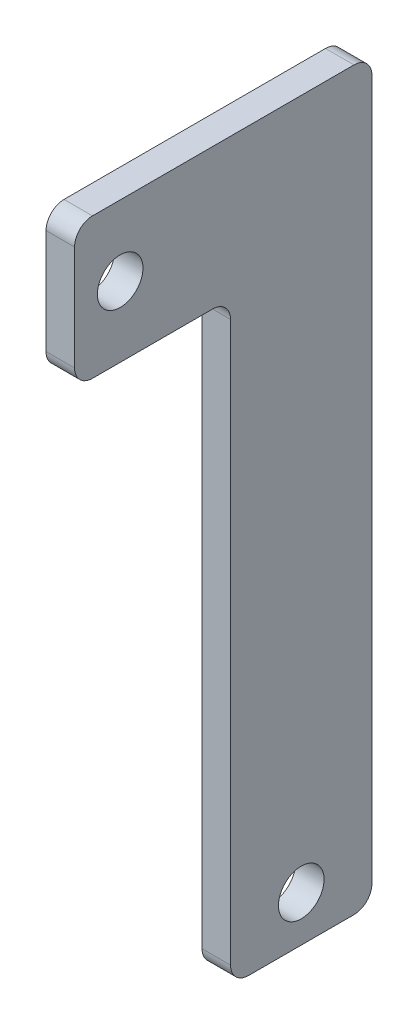
SolidWorks part; units mm, degrees
material "Custom Plastic"
ref_plane "X-Y Datum" through (0, 0, 0) normal (0, 0, 1) x (1, 0, 0)
ref_plane "X-Z Datum" through (0, 0, 0) normal (0, 1, 0) x (1, 0, 0)
ref_plane "Y-Z Datum" through (0, 0, 0) normal (1, 0, 0) x (0, 0, -1)
sketch "Sketch2" plane through (-49.425, 0, 0) normal (1, 0, 0) x (0, 0, -1)
  line L10 (-94.0054, 127.9174) -> (-109.7493, 127.9174)
  line L11 (-94.0054, 127.9174) -> (-94.0054, 209.8686)
  line L12 (-94.0054, 209.8686) -> (-109.7493, 209.8686)
  line L13 (-109.7493, 127.9174) -> (-109.7493, 194.1974)
  line L14 (-109.7493, 209.8686) -> (-127.123, 209.8686)
  line L16 (-109.7493, 194.1974) -> (-127.123, 194.1974)
  line L17 (-127.123, 209.8686) -> (-127.123, 194.1974)
base flange "Base-Flange1" sketch "Sketch2" thickness 3.175 reverse thickness direction yes parameters "D1"=10
sketch "Sketch9" plane through (-49.425, 0, 0) normal (-1, 0, 0) x (0, 0, 1)
  line L0 (127.123, 202.033) -> (122.043, 202.033)
  line L1 (127.123, 209.8686) -> (127.123, 194.1974) construction
  line L2 (101.8774, 127.9174) -> (101.8774, 132.9974)
  line L3 (109.7493, 127.9174) -> (94.0054, 127.9174) construction
  circle A0 centre (122.043, 202.033) radius 2.54
  circle A1 centre (101.8774, 132.9974) radius 2.54
extrude "Cut-Extrude2" cut sketch "Sketch9" against normal through all
fillet "Fillet1" radius 2 6 edges at (-47.8375, 127.9174, 109.7493) (-47.8375, 127.9174, 94.0054) (-47.8375, 209.8686, 94.0054) (-47.8375, 194.1974, 109.7493) (-47.8375, 194.1974, 127.123) (-47.8375, 209.8686, 127.123)
sketch "Bend-Lines1" [suppressed] plane through (0, 0, 0) normal (0, 1, 0) x (1, 0, 0)
sketch "Bounding-Box1" [suppressed] plane through (0, 0, 0) normal (0, 1, 0) x (1, 0, 0)
sheet metal parameters "Sheet-Metal1" thickness 3.175 parameters "D1"=10
flat pattern "Flat-Pattern1" [suppressed]
sketch "Bend-Lines2" plane through (0, 0, 0) normal (0, 1, 0) x (1, 0, 0)
sketch3d "Bounding-Box2" [suppressed]
  line L0 (94.0054, 127.9174, 0) -> (94.0054, 209.8686, 0) construction
  line L1 (127.123, 127.9174, 0) -> (127.123, 209.8686, 0) construction
  line L2 (94.0054, 127.9174, 0) -> (127.123, 127.9174, 0) construction
  line L3 (94.0054, 209.8686, 0) -> (127.123, 209.8686, 0) construction
sketch "Sketch7-1" [suppressed] plane through (-46.25, 0, 0) normal (1, 0, 0) x (0, 0, -1)
  circle A3 centre (-122.8663, 199.3105) radius 3
  circle A5 centre (-103.3663, 134.005) radius 4
sheet metal parameters "Sheet-Metal3" thickness 3.175 parameters "D1"=10
flat pattern "Flat-Pattern1"
sketch "Bend-Lines2" plane through (0, 0, 0) normal (0, 1, 0) x (1, 0, 0)
sketch3d "Bounding-Box2" [suppressed]
  line L0 (94.0054, 127.9174, 0) -> (94.0054, 209.8686, 0) construction
  line L1 (127.123, 127.9174, 0) -> (127.123, 209.8686, 0) construction
  line L2 (94.0054, 127.9174, 0) -> (127.123, 127.9174, 0) construction
  line L3 (94.0054, 209.8686, 0) -> (127.123, 209.8686, 0) construction
